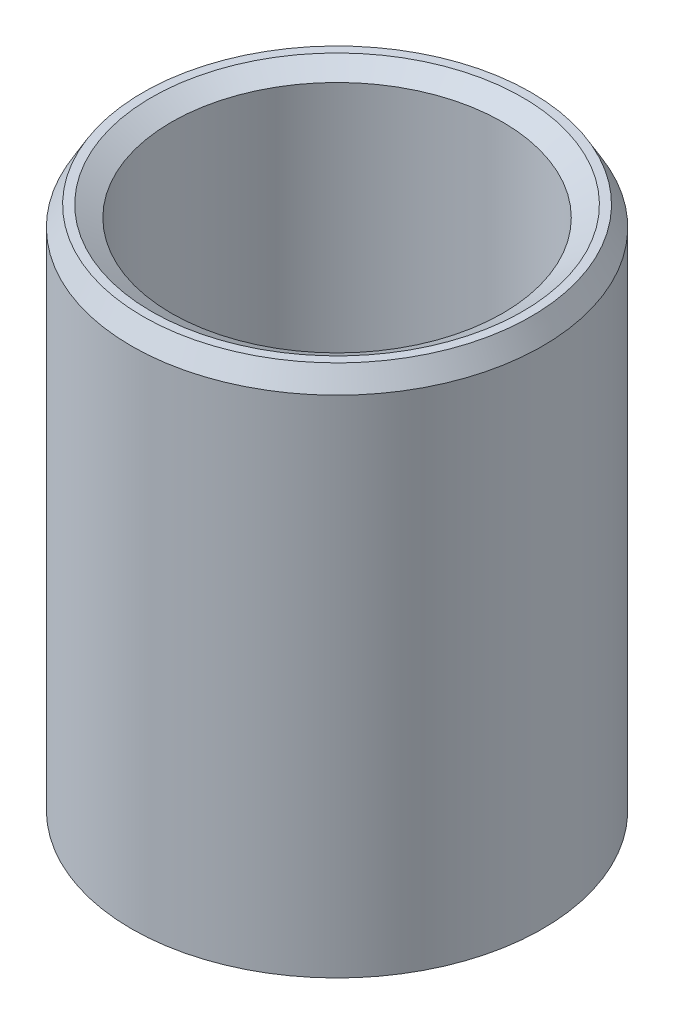
SolidWorks part; units mm, degrees
ref_plane "Front Plane" through (0, 0, 0) normal (0, 0, 1) x (1, 0, 0)
ref_plane "Top Plane" through (0, 0, 0) normal (0, 1, 0) x (1, 0, 0)
ref_plane "Right Plane" through (0, 0, 0) normal (1, 0, 0) x (0, 0, -1)
sketch "Sketch1" plane through (0, 0, 0) normal (0, 1, 0) x (1, 0, 0)
  circle A0 centre (0, 0) radius 35
  dimension "SLEEVE_OD" = 70
extrude "Boss-Extrude1" add sketch "Sketch1" along normal blind 91.2671
sketch "Sketch2" plane through (0, 0, 0) normal (0, 1, 0) x (1, 0, 0)
  circle A0 centre (0, 0) radius 28.2023
  dimension "BORE_D" = 56.4046
extrude "Cut-Extrude1" cut sketch "Sketch2" along normal through all
chamfer "Chamfer1" distance 3.3836 angle 30 4 edges at (0, 91.2671, 28.2023) (0, 0, 28.2023) (0, 0, 35) (0, 91.2671, 35) first distance on face at (0, 91.2671, 28.2023) first distance on face at (0, 0, 28.2023) first distance on face at (0, 91.2671, 35)
